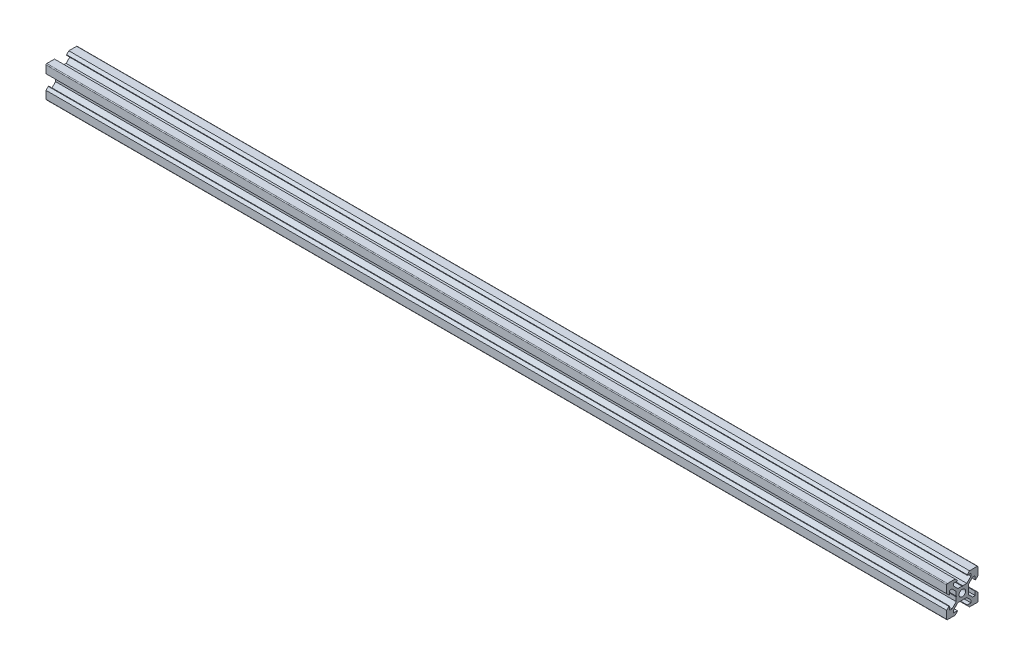
SolidWorks part; units mm, degrees
material "6061-T6 (SS)"
ref_plane "Top" through (0, 0, 0) normal (0, 0, 1) x (1, 0, 0)
ref_plane "Front" through (0, 0, 0) normal (0, 1, 0) x (1, 0, 0)
ref_plane "Right" through (0, 0, 0) normal (1, 0, 0) x (0, 0, -1)
sketch "Profile Sketch" plane through (0, 0, 0) normal (1, 0, 0) x (0, 0, -1)
  line L0 (-0.5, 10) -> (-5.42, 10)
  line L1 (-4.5, 8.2) -> (-4.5, 6.56)
  line L2 (-4.5, 6.56) -> (-7.16, 3.9)
  line L3 (-7.16, 3.9) -> (-9.79, 3.9)
  line L4 (-9.79, 3.9) -> (-10, 3.69)
  line L7 (-3.4387, 5.5) -> (-6.1, 2.8387)
  line L8 (-6.1, 2.8387) -> (-6.1, -0.21)
  line L9 (-6.875, 8.545) -> (-6.875, 8.2)
  line L10 (-6.875, 8.2) -> (-4.5, 8.2)
  line L11 (-6.875, 8.545) -> (-5.42, 10)
  line L12 (0, -10) -> (0, 10) construction
  line L13 (-20, 0) -> (20, 0) construction
  line L14 (-10, -10) -> (-10, 10) construction
  line L15 (-6.875, -8.545) -> (-5.42, -10)
  line L16 (-6.875, -8.2) -> (-4.5, -8.2)
  line L17 (-6.875, -8.545) -> (-6.875, -8.2)
  line L18 (-3.44, -5.5) -> (-6.1, -2.8387)
  line L21 (-7.16, -3.9) -> (-9.79, -3.9)
  line L22 (-4.5, -6.56) -> (-7.16, -3.9)
  line L23 (-4.5, -8.2) -> (-4.5, -6.56)
  line L24 (-0.5, -10) -> (-5.42, -10)
  line L25 (-10, 0) -> (-20, 10) construction
  line L26 (-18.545, 3.125) -> (-18.2, 3.125)
  line L27 (-13.125, -8.545) -> (-13.125, -8.2)
  line L28 (-13.125, -8.2) -> (-15.5, -8.2)
  line L29 (-13.125, -8.545) -> (-14.58, -10)
  line L30 (-15.5, -8.2) -> (-15.5, -6.56)
  line L31 (-15.5, -6.56) -> (-12.84, -3.9)
  line L32 (-12.84, -3.9) -> (-10.21, -3.9)
  line L33 (-20, 4.58) -> (-20, 9.5)
  line L34 (-13.9, 2.8387) -> (-13.9, 0.21)
  line L35 (-16.56, 5.5) -> (-13.9, 2.8387)
  line L36 (-12.84, 3.9) -> (-10.21, 3.9)
  line L37 (-15.5, 6.56) -> (-12.84, 3.9)
  line L38 (-15.5, 8.2) -> (-15.5, 6.56)
  line L39 (-13.125, 8.545) -> (-14.58, 10)
  line L40 (-13.125, 8.2) -> (-15.5, 8.2)
  line L41 (-13.125, 8.545) -> (-13.125, 8.2)
  line L42 (-18.2, 3.125) -> (-18.2, 5.5)
  line L43 (-18.545, 3.125) -> (-20, 4.58)
  line L44 (-18.2, 5.5) -> (-16.56, 5.5)
  line L45 (-14.58, 10) -> (-19.5, 10)
  line L46 (-16.56, -5.5) -> (-13.9, -2.8387)
  line L47 (-14.58, -10) -> (-19.5, -10)
  line L48 (-18.2, -5.5) -> (-16.56, -5.5)
  line L49 (-18.545, -3.125) -> (-20, -4.58)
  line L50 (-18.2, -3.125) -> (-18.2, -5.5)
  line L51 (-20, -4.58) -> (-20, -9.5)
  line L52 (-18.545, -3.125) -> (-18.2, -3.125)
  line L53 (10, -10) -> (10, 10) construction
  line L99 (-10, 3.69) -> (-10.21, 3.9)
  line L100 (-10, -3.69) -> (-10.21, -3.9)
  line L101 (-9.79, -3.9) -> (-10, -3.69)
  line L102 (-13.9, -0.21) -> (-13.69, 0)
  line L103 (-13.69, 0) -> (-13.9, 0.21)
  line L104 (-13.9, -0.21) -> (-13.9, -2.8387)
  line L105 (-6.1, -0.21) -> (-6.31, 0)
  line L106 (-6.31, 0) -> (-6.1, -0.21)
  line L107 (-6.1, -0.21) -> (-6.1, -2.8387)
  line L117 (-5.42, -10) -> (-0.5, -10)
  line L118 (20, -10) -> (20, 10) construction
  line L119 (20, -10) -> (-20, -10) construction
  line L120 (-20, -10) -> (-20, 10) construction
  line L121 (20, 10) -> (-20, 10) construction
  line L122 (20, -10) -> (-20, 10) construction
  line L123 (-20, -10) -> (20, 10) construction
  line L124 (-5.42, 10) -> (-0.5, 10)
  line L125 (-1.455, 3.125) -> (-1.8, 3.125)
  line L126 (-1.455, -3.125) -> (-1.8, -3.125)
  line L127 (-1.8, -5.5) -> (-3.44, -5.5)
  line L128 (-1.8, 5.5) -> (-3.44, 5.5)
  line L129 (-1.8, 3.125) -> (-1.8, 5.5)
  line L130 (-1.8, -3.125) -> (-1.8, -5.5)
  line L131 (0, -4.58) -> (0, -9.5)
  line L132 (0, 4.58) -> (0, 9.5)
  line L133 (-1.455, 3.125) -> (0, 4.58)
  line L134 (-1.455, -3.125) -> (0, -4.58)
  circle A0 centre (-10, 0) radius 2.1
  arc A1 (-19.5, 10) -> (-20, 9.5) centre (-19.5, 9.5) ccw
  arc A2 (-19.5, -10) -> (-20, -9.5) centre (-19.5, -9.5) cw
  arc A3 (-0.5, -10) -> (0, -9.5) centre (-0.5, -9.5) ccw
  arc A4 (-0.5, 10) -> (0, 9.5) centre (-0.5, 9.5) cw
  point P2 (-17.38, 5.5)
  point P35 (-2.4957, 0)
  point P76 (-2.62, 5.5)
  point P108 (0, -8.2)
  point P119 (0, 8.2)
  point P131 (0, 0)
  point P143 (0, 0)
  dimension "D4" = 5.42
  dimension "D5" = 40
  dimension "D6" = 4.2
  dimension "D16" = 0.5
  dimension "D1" = 0.21
  dimension "D2" = 45
  dimension "D3" = 20
  dimension "D7" = 1.5
  dimension "D8" = 1.8
  dimension "D9" = 10
  dimension "D10" = 3.9
  dimension "D11" = 3.9
  dimension "D13" = 3.125
  dimension "D14" = 5.5
  dimension "D15" = 1.64
extrude "Profile Extrude" add sketch "Profile Sketch" along normal blind 575 contours L126 L0 L11 L9 L10 L1 L2 L3 L4 L99 L36 L37 L38 L40 L41 L39 L45 A1 L33 L43 L26 L42 L44 L35 L34 L103 L102 L104 L46 L48 L50 L52 L49 L51 A2 L47 region at (0, 9.6536, 0.3464)
equation "\"M2x0.4_Close_Hole\"= 2.2"
equation "\"M2.5x0.45_Close_Hole\"= 2.7"
equation "\"M3x0.5_Close_Hole\"= 3.2"
equation "\"M4x0.7_Close_Hole\"= 4.3"
equation "\"M5x0.8_Close_Hole\"= 5.3"
equation "\"M6x1_Close_Hole\"= 6.3"
equation "\"M7x1_Close_Hole\"= 7.4"
equation "\"M8x1.25_Close_Hole\"= 8.4"
equation "\"M2x0.4_Tap_Hole_75\"= 1.6"
equation "\"M3x0.5_Tap_Hole_75\"= 2.5"
equation "\"M4x0.7_Tap_Hole_75\"= 3.3"
equation "\"M5x0.8_Tap_Hole_75\"= 4.2"
equation "\"M6x1_Tap_Hole_75\"= 5"
equation "\"M7x1_Tap_Hole_75\"= 6"
equation "\"M8x1.25_Tap_Hole_75\"= 6.8"
